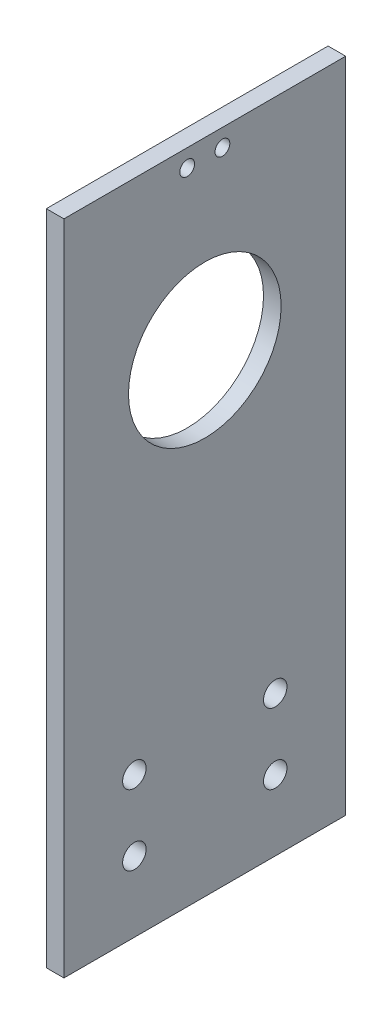
SolidWorks part; units mm, degrees
material "6061 Alloy"
ref_plane "Front Plane" through (0, 0, 0) normal (0, 0, 1) x (1, 0, 0)
ref_plane "Top Plane" through (0, 0, 0) normal (0, 1, 0) x (1, 0, 0)
ref_plane "Right Plane" through (0, 0, 0) normal (1, 0, 0) x (0, 0, -1)
sketch "Sketch1" plane through (0, 0, 0) normal (1, 0, 0) x (0, 0, -1)
  line L1 (-38.1, 88.9) -> (38.1, 88.9)
  line L2 (-38.1, 88.9) -> (-38.1, -88.9)
  line L3 (-38.1, -88.9) -> (38.1, -88.9)
  line L4 (38.1, 88.9) -> (38.1, -88.9)
  line L5 (-38.1, 88.9) -> (38.1, -88.9) construction
  line L6 (-38.1, -88.9) -> (38.1, 88.9) construction
  point P0 (0, 0)
  dimension "D1" = 177.8
  dimension "D2" = 76.2
extrude "Boss-Extrude1" add sketch "Sketch1" along normal blind 4.7625
sketch "Sketch2" plane through (4.7625, 0, 0) normal (1, 0, 0) x (0, 0, -1)
  line L0 (-38.1, -88.9) -> (38.1, -88.9) construction
  line L1 (-38.1, 88.9) -> (-38.1, -88.9) construction
  circle A0 centre (0, 39.116) radius 20.6375
  dimension "D1" = 128.016
  dimension "D2" = 38.1
  dimension "D3" = 41.275
extrude "Cut-Extrude1" cut sketch "Sketch2" against normal up to next
sketch "Sketch4" plane through (4.7625, 0, 0) normal (1, 0, 0) x (0, 0, -1)
  line L0 (-38.1, 88.9) -> (-38.1, -88.9) construction
  line L1 (-38.1, -88.9) -> (38.1, -88.9) construction
  circle A0 centre (-19.05, -50.8) radius 3.175
  circle A1 centre (19.05, -50.8) radius 3.175
  circle A2 centre (19.05, -69.85) radius 3.175
  circle A3 centre (-19.05, -69.85) radius 3.175
  dimension "D1" = 19.05
  dimension "D2" = 6.35
  dimension "D3" = 38.1
  dimension "D5" = 2
  dimension "D4" = 2
extrude "Cut-Extrude2" cut sketch "Sketch4" against normal up to next
sketch "Sketch5" plane through (4.7625, 0, 0) normal (1, 0, 0) x (0, 0, -1)
  circle A0 centre (-4.7625, 84.1375) radius 2 construction
  circle A1 centre (4.7625, 84.1375) radius 2 construction
  circle A2 centre (-4.7625, 84.1375) radius 2
  circle A3 centre (4.7625, 84.1375) radius 2
extrude "Cut-Extrude3" cut sketch "Sketch5" against normal up to next
